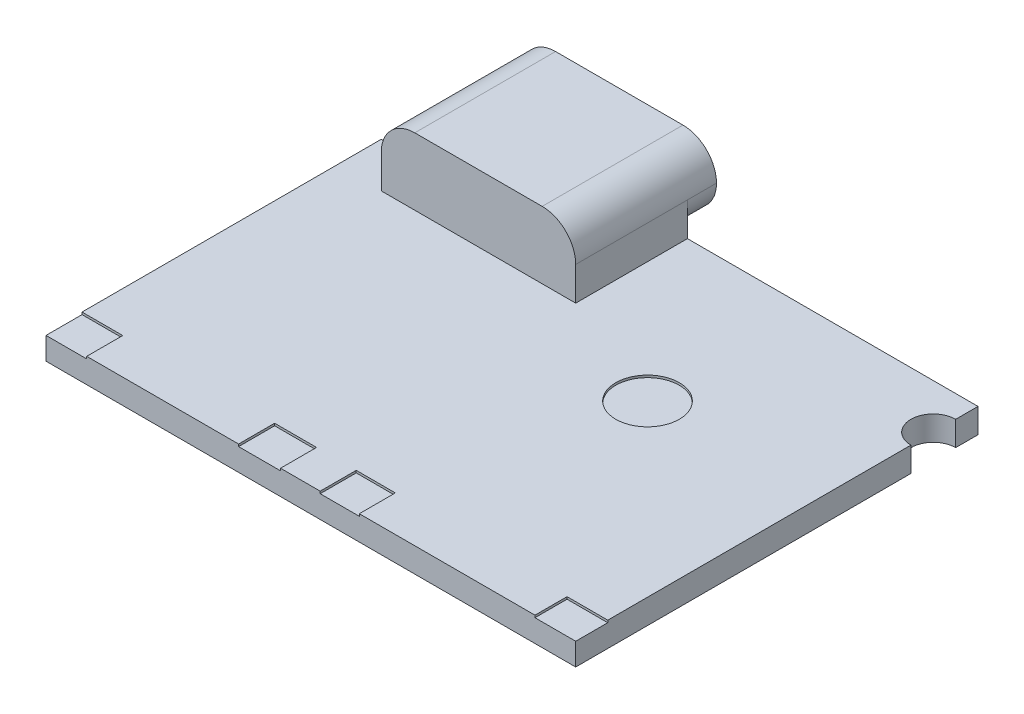
SolidWorks part; units mm, degrees
ref_plane "Plano frontal" through (0, 0, 0) normal (0, 0, 1) x (1, 0, 0)
ref_plane "Plano superior" through (0, 0, 0) normal (0, 1, 0) x (1, 0, 0)
ref_plane "Plano direito" through (0, 0, 0) normal (1, 0, 0) x (0, 0, -1)
sketch "Esboço1" plane through (0, 0, 0) normal (0, 1, 0) x (1, 0, 0)
  line L1 (0, 0) -> (23.7, 0)
  line L2 (0, 0) -> (0, 18)
  line L3 (0, 18) -> (23.7, 18)
  line L4 (23.7, 0) -> (23.7, 18)
  dimension "D1" = 23.7
  dimension "D2" = 18
extrude "Ressalto-extrusão1" add sketch "Esboço1" along normal blind 1.1
sketch "Esboço2" plane through (0, 1.1, 0) normal (0, 1, 0) x (1, 0, 0)
  line L0 (23.7, 0) -> (23.7, 18) construction
  line L1 (2, 19.3) -> (10.7, 19.3)
  line L2 (2, 19.3) -> (2, 13)
  line L3 (2, 13) -> (10.7, 13)
  line L4 (10.7, 19.3) -> (10.7, 13)
  line L5 (23.7, 18) -> (0, 18) construction
  dimension "D1" = 8.7
  dimension "D2" = 21.7
  dimension "D3" = 1.3
  dimension "D4" = 6.3
extrude "Ressalto-extrusão2" add sketch "Esboço2" along normal blind 3
fillet "Filete1" radius 1.5 4 edges at (10.7, 1.1, -18.65) (2, 1.1, -18.65) (10.7, 4.1, -16.15) (2, 4.1, -16.15)
sketch "Esboço3" plane through (0, 1.1, 0) normal (0, 1, 0) x (1, 0, 0)
  line L0 (0, 0) -> (23.7, 0) construction
  line L1 (0, 0) -> (1.8213, 0)
  line L2 (0, 0) -> (0, 1.6118)
  line L3 (0, 1.6118) -> (1.8213, 1.6118)
  line L4 (1.8213, 0) -> (1.8213, 1.6118)
  line L5 (8.617, 0) -> (10.4934, 0)
  line L6 (8.617, 0) -> (8.617, 1.6118)
  line L7 (8.617, 1.6118) -> (10.4934, 1.6118)
  line L8 (10.4934, 0) -> (10.4934, 1.6118)
  line L10 (12.2684, 0) -> (14.018, 0)
  line L11 (12.2684, 0) -> (12.2684, 1.6118)
  line L12 (12.2684, 1.6118) -> (14.018, 1.6118)
  line L13 (14.018, 0) -> (14.018, 1.6118)
  line L14 (23.7, 0) -> (21.8787, 0)
  line L15 (23.7, 0) -> (23.7, 1.4343)
  line L16 (23.7, 1.4343) -> (21.8787, 1.4343)
  line L17 (21.8787, 0) -> (21.8787, 1.4343)
  circle A0 centre (16.0973, 10.8164) radius 1.4202
extrude "Corte-extrusão1" cut sketch "Esboço3" against normal blind 0.1 contours A0 | L2 L1 L4 L3 | L6 L5 L8 L7 | L11 L10 L13 L12 | L15 L14 L17 L16
sketch "Esboço4" plane through (0, 1.1, 0) normal (0, 1, 0) x (1, 0, 0)
  line L0 (0, 18) -> (0, 1.6118) construction
  line L1 (23.7, 1.4343) -> (23.7, 18) construction
  line L2 (0, 16) -> (23.7, 16) construction
  line L3 (23.7, 18) -> (10.7, 18) construction
  circle A0 centre (0, 16) radius 1
  circle A1 centre (23.7, 16) radius 1
  dimension "D1" = 2
  dimension "D2" = 2
extrude "Corte-extrusão2" cut sketch "Esboço4" against normal through all
